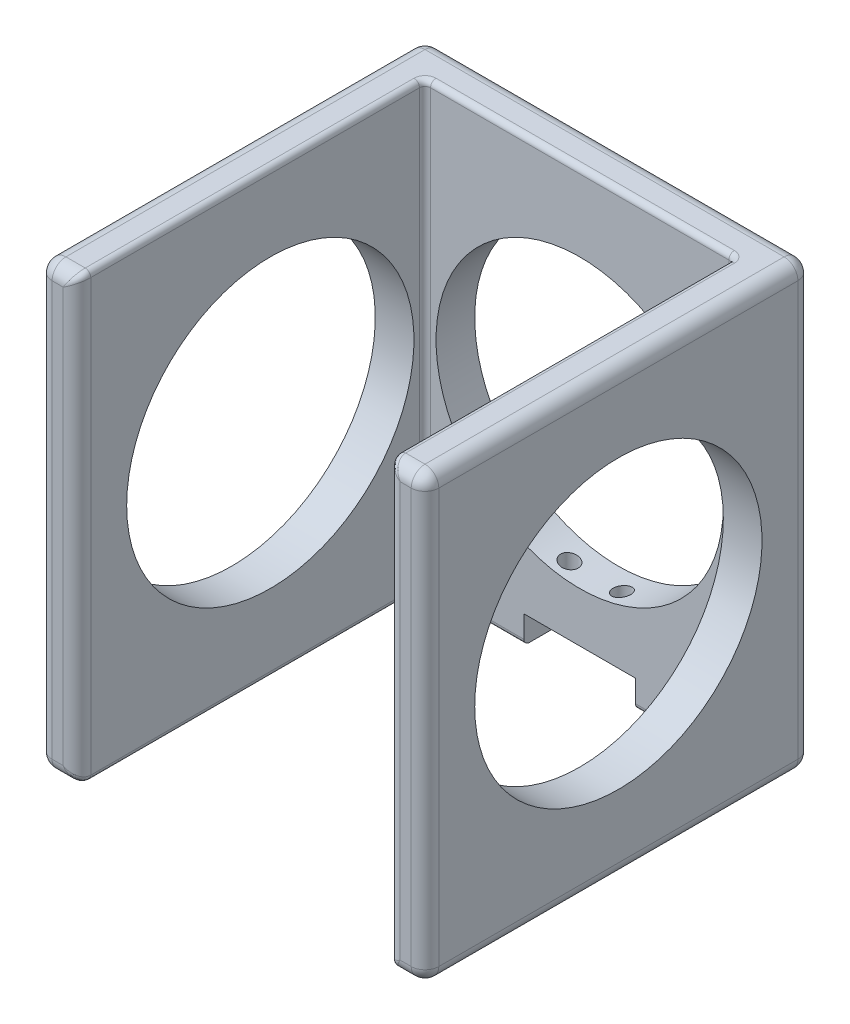
SolidWorks part; units mm, degrees
ref_plane "Front Plane" through (0, 0, 0) normal (0, 0, 1) x (1, 0, 0)
ref_plane "Top Plane" through (0, 0, 0) normal (0, 1, 0) x (1, 0, 0)
ref_plane "Right Plane" through (0, 0, 0) normal (1, 0, 0) x (0, 0, -1)
sketch "Sketch1" plane through (0, 0, 0) normal (0, 1, 0) x (1, 0, 0)
  line L0 (0, 35) -> (70, 35) construction
  line L1 (0, 0) -> (70, 0)
  line L2 (0, 0) -> (0, 70)
  line L3 (0, 70) -> (70, 70)
  line L4 (70, 0) -> (70, 70)
  dimension "D1" = 70
  dimension "D2" = 70
extrude "Outer Housing" add sketch "Sketch1" along normal blind 80
sketch "Sketch2" plane through (0, 80, 0) normal (0, 1, 0) x (1, 0, 0)
  line L0 (7, 0) -> (7, 70) construction
  line L1 (0, 0) -> (70, 0) construction
  line L2 (70, 70) -> (0, 70) construction
  line L3 (0, 70) -> (0, 0) construction
  line L4 (63, 70) -> (63, 0) construction
  line L5 (70, 0) -> (70, 70) construction
  line L6 (7, 63) -> (63, 63) construction
  line L7 (7, 0) -> (7, 63)
  line L8 (7, 63) -> (63, 63)
  line L9 (63, 63) -> (63, 0)
  line L10 (7, 0) -> (63, 0)
  dimension "D1" = 7
  dimension "D2" = 7
  dimension "D3" = 7
extrude "Cut-Extrude2" cut sketch "Sketch2" against normal through all
sketch "Sketch3" plane through (0, 0, 0) normal (-1, 0, 0) x (0, 0, 1)
  line L0 (-70, 40) -> (0, 40) construction
  line L1 (-70, 80) -> (-70, 0) construction
  line L2 (0, 80) -> (0, 0) construction
  line L3 (-35, 15.8781) -> (-35, 58.0416) construction
  circle A0 centre (-35, 40) radius 26
  dimension "D1" = 52
  dimension "D2" = 35
extrude "Cut-Extrude3" cut sketch "Sketch3" against normal through all
sketch "Sketch4" plane through (0, 0, -63) normal (0, 0, 1) x (1, 0, 0)
  line L0 (7, 80) -> (63, 0) construction
  circle A0 centre (35, 40) radius 26
  dimension "D1" = 52
extrude "Cut-Extrude4" cut sketch "Sketch4" against normal through all
fillet "In-Fillet" radius 1 2 edges at (63, 40, -63) (7, 40, -63)
fillet "Fillet2" radius 1 10 edges at (63, 0, -31) (62.7071, 0, -62.7071) (7, 0, -31) (7.2929, 0, -62.7071) (63, 80, -31) (62.7071, 80, -62.7071) (7, 80, -31) (7.2929, 80, -62.7071) (35, 0, -63) (35, 80, -63)
fillet "Fillet3" radius 2.5 20 edges at (67, 0, 0) (63.2929, 0.2929, 0) (67, 80, 0) (63.2929, 79.7071, 0) (0, 40, 0) (3, 80, 0) (6.7071, 79.7071, 0) (7, 40, 0) (6.7071, 0.2929, 0) (3, 0, 0) (63, 40, 0) (70, 40, 0) (70, 0, -35) (70, 40, -70) (35, 0, -70) (0, 0, -35) (0, 40, -70) (0, 80, -35) (35, 80, -70) (70, 80, -35)
ref_plane "Plane1" through (35, 0, 0) normal (1, 0, 0) x (0, 0, -1)
sketch "Sketch5" plane through (0, 0, 0) normal (0, -1, 0) x (1, 0, 0)
  line L0 (2.5, -67.5) -> (67.5, -67.5) construction
  line L1 (24.9, -70) -> (45.1, -70)
  line L2 (24.9, -70) -> (24.9, -63)
  line L3 (24.9, -63) -> (45.1, -63)
  line L4 (45.1, -70) -> (45.1, -63)
  line L5 (8, -63) -> (62, -63) construction
  line L6 (67.5, -70) -> (2.5, -70) construction
  line L7 (35, -67.5) -> (35, -66.0608) construction
  line L8 (45.1, -63) -> (24.9, -70) construction
  line L9 (35, -32.725) -> (35, 32.725) construction
  circle A0 centre (39.75, -65.9) radius 1.6
  circle A1 centre (30.25, -65.9) radius 1.6
  point P0 (35, -67.5)
  point P8 (35, -66.5)
  point P16 (0, 0)
  point P17 (0, 0)
  point P18 (0, 0)
  point P19 (35, -66.5)
  point P22 (39.75, -66.8201)
  point P25 (39.75, -67.1)
  line M11 (62, -64) -> (8, -64)
  line M16 (2.5, -67.5) -> (67.5, -67.5)
  dimension "D1" = 4.75
  dimension "D2" = 3.2
  dimension "D4" = 4.1
  dimension "D3" = 20.2
extrude "Cut-Extrude5" cut sketch "Sketch5" against normal blind 5 contours L1 L4 L2 M16 | A1 A0 L4 L2 M16 M11 | L4 L3 L2 M11 | A0 | A1 region at (35, 0, -68.75) region at (30.25, 0, -65.9) region at (39.75, 0, -65.9) region at (35, 0, -65.7058) region at (35, 0, -63.5)
extrude "Cut-Extrude6" cut sketch "Sketch5<3>" against normal blind 17.4 contours A1 | A0 region at (39.75, 0, -65.9) region at (30.25, 0, -65.9)
sketch "Sketch5<3>" plane through (0, 0, 0) normal (0, -1, 0) x (1, 0, 0) same geometry as "Sketch5"
equation "\"D2@Sketch1\"=70"
